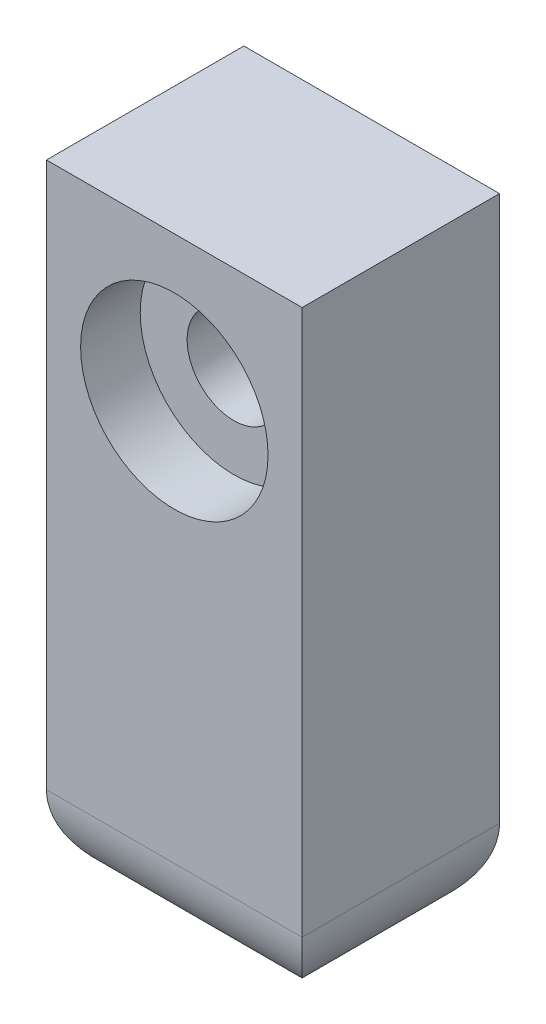
SolidWorks part; units mm, degrees
ref_plane "Front Plane" through (0, 0, 0) normal (0, 0, 1) x (1, 0, 0)
ref_plane "Top Plane" through (0, 0, 0) normal (0, 1, 0) x (1, 0, 0)
ref_plane "Right Plane" through (0, 0, 0) normal (1, 0, 0) x (0, 0, -1)
sketch "Sketch1" plane through (0, 0, 0) normal (0, 0, 1) x (1, 0, 0)
  line L0 (-15, -17) -> (0, 0) construction
  line L1 (-15, 57.0003) -> (15, 57.0003)
  line L2 (-15, 57.0003) -> (-15, -17)
  line L3 (-15, -17) -> (15, -17)
  line L4 (15, 57.0003) -> (15, -17)
  line L5 (0, 0) -> (15, -17) construction
  line L6 (-15, 57.0003) -> (0, 40.0003) construction
  line L7 (0, 40.0003) -> (15, 57.0003) construction
  circle A0 centre (0, 0) radius 7.9823
  circle A1 centre (0, 40.0003) radius 11
  dimension "D3" = 30
  dimension "D4" = 22
  dimension "D5" = 15.9646
  dimension "D1" = 40.0003
  dimension "D2" = 17
extrude "Boss-Extrude1" add sketch "Sketch1" along normal blind 23.1638
sketch "Sketch2" plane through (0, 0, 23.1638) normal (0, 0, 1) x (1, 0, 0)
  circle A0 centre (0, 0) radius 4
  circle A1 centre (0, 0) radius 7.9823 construction
  circle A2 centre (0, 0) radius 7.9823
  dimension "D1" = 8
extrude "Boss-Extrude2" add sketch "Sketch2" against normal up to surface (23.1638 mm away) up to face at (0, 20.0001, 0)
sketch "Sketch3" plane through (0, 0, 23.1638) normal (0, 0, 1) x (1, 0, 0)
  circle A0 centre (0, 0) radius 4
extrude "Boss-Extrude3" add sketch "Sketch3" against normal blind 32.1638
sketch "Sketch4" plane through (0, 0, 0) normal (0, 0, -1) x (-1, 0, 0)
  circle A0 centre (0, 40.0003) radius 11 construction
  circle A1 centre (0, 40.0003) radius 11
  circle A2 centre (0, 40.0003) radius 5.5
  dimension "D1" = 5.5
extrude "Boss-Extrude4" add sketch "Sketch4" against normal blind 16.1638
fillet "Fillet1" radius 10 4 edges at (-15, -17, 11.5819) (0, -17, 23.1638) (15, -17, 11.5819) (0, -17, 0)
